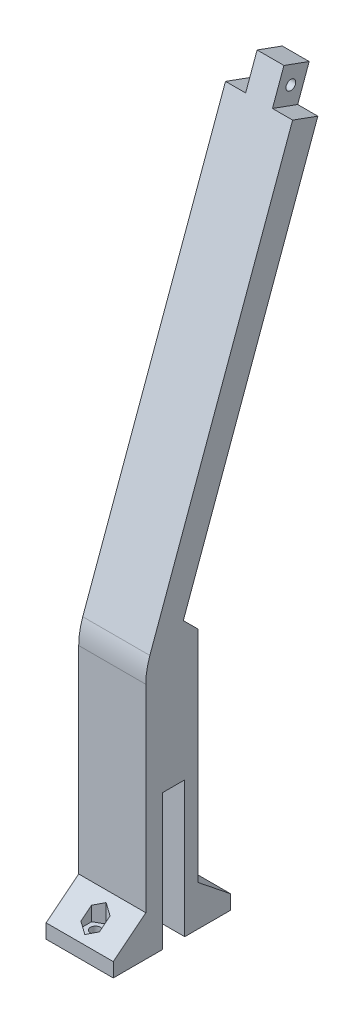
SolidWorks part; units mm, degrees
ref_plane "Front Plane" through (0, 0, 0) normal (0, 0, 1) x (1, 0, 0)
ref_plane "Top Plane" through (0, 0, 0) normal (0, 1, 0) x (1, 0, 0)
ref_plane "Right Plane" through (0, 0, 0) normal (1, 0, 0) x (0, 0, -1)
sketch "Sketch2" plane through (0, 0, 0) normal (1, 0, 0) x (0, 0, -1)
  line L0 (36.0729, 122.5) -> (-51.2799, -117.5)
  line L1 (-51.2799, -117.5) -> (-51.2799, -192)
  line L5 (-42.7665, -117.5) -> (42.7665, 117.5)
  line L6 (192.7665, 122.5) -> (36.0729, 122.5)
  line L7 (-42.7665, -117.5) -> (-35.6799, -117.5)
  line L9 (-39.6799, -151.5) -> (-46.2799, -151.5)
  line L10 (-46.2799, -151.5) -> (-46.2799, -192)
  line L13 (-35.6799, -117.5) -> (-35.6799, -192)
  line L14 (-35.6799, -192) -> (-39.6799, -192)
  line L15 (-39.6799, -192) -> (-39.6799, -151.5)
  line L16 (-51.2799, -192) -> (-46.2799, -192)
  line L18 (192.7665, 122.5) -> (192.7665, 117.5)
  line L19 (192.7665, 117.5) -> (42.7665, 117.5)
  dimension "D1" = 34
  dimension "D2" = 4
  dimension "D3" = 5
  dimension "D4" = 6.6
  dimension "D5" = 150
  dimension "D6" = 5
  dimension "D7" = 40.5
  dimension "D9" = 240
  dimension "D10" = 8
  dimension "D11" = 70
extrude "Boss-Extrude1" add sketch "Sketch2" along normal mid plane 20
chamfer "Chamfer1" distance 10 angle 45 1 edges at (0, -117.5, 42.7665) first distance on face at (0, -117.5, 39.2232)
sketch "Sketch6" plane through (10, 0, 0) normal (1, 0, 0) x (0, 0, -1)
  line L0 (-51.2799, -180) -> (-66.2799, -192)
  line L1 (-66.2799, -192) -> (-51.2799, -192)
  line L2 (-51.2799, -192) -> (-51.2799, -180)
  line L3 (-51.2799, -117.5) -> (-51.2799, -192) construction
  line L4 (-35.6799, -192) -> (-20.6799, -192)
  line L5 (-20.6799, -192) -> (-35.6799, -180)
  line L6 (-35.6799, -192) -> (-35.6799, -114.5866) construction
  line L7 (-35.6799, -180) -> (-35.6799, -192)
  dimension "D1" = 15
  dimension "D2" = 12
extrude "Boss-Extrude2" add sketch "Sketch6" against normal up to vertex (20 mm away) up to point (-10, -192, 51.2799)
sketch "Sketch7" plane through (0, -192, 0) normal (0, -1, 0) x (-1, 0, 0)
  line L0 (0, -66.2799) -> (0, -46.2799) construction
  line L1 (10, -66.2799) -> (-10, -66.2799) construction
  line L2 (-10, -46.2799) -> (10, -46.2799) construction
  line L3 (0, -20.6799) -> (0, -39.6799) construction
  line L4 (10, -20.6799) -> (-10, -20.6799) construction
  line L5 (-10, -39.6799) -> (10, -39.6799) construction
  circle A0 centre (0, -56.2799) radius 1.5
  circle A1 centre (0, -30.1799) radius 1.5
  dimension "D1" = 3
  dimension "D2" = 3
extrude "Cut-Extrude1" cut sketch "Sketch7" against normal blind 20
ref_plane "Plane1" through (0, -187, 0) normal (0, -1, 0) x (-1, 0, 0)
sketch "Sketch9" plane through (0, -187, 0) normal (0, -1, 0) x (-1, 0, 0)
  line L1 (2.75, -57.8676) -> (2.75, -54.6922)
  line L2 (2.75, -54.6922) -> (0, -53.1045)
  line L3 (0, -53.1045) -> (-2.75, -54.6922)
  line L4 (-2.75, -54.6922) -> (-2.75, -57.8676)
  line L5 (-2.75, -57.8676) -> (0, -59.4554)
  line L6 (0, -59.4554) -> (2.75, -57.8676)
  line L7 (2.75, -31.7676) -> (2.75, -28.5922)
  line L8 (2.75, -28.5922) -> (0, -27.0045)
  line L9 (0, -27.0045) -> (-2.75, -28.5922)
  line L10 (-2.75, -28.5922) -> (-2.75, -31.7676)
  line L11 (-2.75, -31.7676) -> (0, -33.3554)
  line L12 (0, -33.3554) -> (2.75, -31.7676)
  circle A0 centre (0, -56.2799) radius 2.75 construction
  circle A1 centre (0, -30.1799) radius 2.75 construction
  dimension "D1" = 5.5
  dimension "D2" = 5.5
extrude "Cut-Extrude3" cut sketch "Sketch9" against normal blind 20
fillet "Fillet5" radius 20 1 edges at (0, -117.5, 51.2799)
fillet "Fillet6" radius 10 1 edges at (0, 122.5, -36.0729)
sketch "Sketch10" plane through (10, 0, 0) normal (1, 0, 0) x (0, 0, -1)
  line L0 (-51.2799, -180) -> (-66.2799, -192) construction
  line L1 (-66.2799, -192) -> (-60.9799, -192)
  line L2 (-66.2799, -192) -> (-66.2799, -187.76)
  line L3 (-66.2799, -187.76) -> (-60.9799, -187.76)
  line L4 (-60.9799, -192) -> (-60.9799, -187.76)
  line L6 (-43.4799, -150) -> (-43.4799, -190.5) construction
  line L8 (-25.9799, -192) -> (-25.9799, -187.76)
  line L9 (-20.6799, -187.76) -> (-25.9799, -187.76)
  line L10 (-20.6799, -192) -> (-20.6799, -187.76)
  line L11 (-20.6799, -192) -> (-25.9799, -192)
  dimension "D1" = 35
extrude "Cut-Extrude4" cut sketch "Sketch10" against normal through all
sketch "Sketch11" plane through (0, 122.5, 0) normal (0, 1, 0) x (1, 0, 0)
  line L5 (-10, 43.075) -> (10, 43.075) construction
  line L6 (-10, 192.7665) -> (-6.25, 192.7665)
  line L7 (-10, 192.7665) -> (-10, 48.075)
  line L8 (-10, 48.075) -> (-6.25, 48.075)
  line L9 (-6.25, 192.7665) -> (-6.25, 48.075)
  line L10 (10, 192.7665) -> (6.25, 192.7665)
  line L11 (10, 192.7665) -> (10, 48.075)
  line L12 (10, 48.075) -> (6.25, 48.075)
  line L13 (6.25, 192.7665) -> (6.25, 48.075)
  dimension "D1" = 12.5
  dimension "D2" = 5
extrude "Cut-Extrude5" cut sketch "Sketch11" against normal through all
sketch "Sketch13" plane through (6.25, 0, 0) normal (1, 0, 0) x (0, 0, -1)
  line L0 (52.7665, 117.5) -> (37.7665, 103.7626)
  line L1 (192.7665, 117.5) -> (48.075, 117.5) construction
  line L2 (-40.098, -110.1685) -> (42.7665, 117.5) construction
  line L3 (37.7665, 103.7626) -> (42.7665, 117.5)
  line L4 (42.7665, 117.5) -> (52.7665, 117.5)
  dimension "D1" = 10
  dimension "D2" = 15
extrude "Boss-Extrude4" add sketch "Sketch13" against normal blind 12.5
sketch "Sketch12" plane through (0, 0, -192.7665) normal (0, 0, -1) x (-1, 0, 0)
  line L0 (-6.25, 117.5) -> (-6.25, 122.5) construction
  line L1 (-6.25, 120.75) -> (-4.25, 120.75)
  line L2 (-6.25, 120.75) -> (-6.25, 119.25)
  line L3 (-6.25, 119.25) -> (-4.25, 119.25)
  line L4 (-4.25, 120.75) -> (-4.25, 119.25)
  line L5 (0, 122.5) -> (0, 117.5) construction
  line L6 (-6.25, 122.5) -> (6.25, 122.5) construction
  line L7 (-6.25, 117.5) -> (6.25, 117.5) construction
  line L8 (4.25, 120.75) -> (4.25, 119.25)
  line L9 (6.25, 119.25) -> (4.25, 119.25)
  line L10 (6.25, 120.75) -> (6.25, 119.25)
  line L11 (6.25, 120.75) -> (4.25, 120.75)
  line L12 (-6.25, 122.5) -> (-6.25, 120.75) construction
  line L13 (-6.25, 117.5) -> (-6.25, 119.25) construction
  dimension "D1" = 1.75
  dimension "D2" = 1.5
  dimension "D3" = 2
extrude "Cut-Extrude6" cut sketch "Sketch12" against normal up to vertex (144.6915 mm away) up to point (10, 122.5, -48.075)
sketch "Sketch14" plane through (10, 0, 0) normal (1, 0, 0) x (0, 0, -1)
  line L0 (-7.5175, 2.7362) -> (0, 0)
  line L1 (33.6781, 115.9202) -> (-50.0738, -114.1861) construction
  line L2 (-7.5175, 2.7362) -> (28.5355, 129.4781)
  line L4 (28.5355, 129.4781) -> (208.2695, 129.4781)
  line L6 (0, 0) -> (208.2695, 117.5864)
  line L7 (208.2695, 117.5864) -> (208.2695, 129.4781)
extrude "Cut-Extrude7" cut sketch "Sketch14" against normal through all
sketch "Sketch15" plane through (0, 2.7362, 7.5175) normal (0, 0.342, 0.9397) x (1, 0, 0)
  line L0 (-10, 0) -> (10, 0) construction
  line L1 (-4, 0) -> (4, 0)
  line L2 (-4, 0) -> (-4, 10)
  line L3 (-4, 10) -> (4, 10)
  line L4 (4, 0) -> (4, 10)
  point P7 (0, 0)
  dimension "D1" = 8
  dimension "5" = 10
extrude "Boss-Extrude5" add sketch "Sketch15" against normal up to vertex (8 mm away) up to point (-10, 0, 0)
sketch "Sketch16" plane through (10, 0, 0) normal (1, 0, 0) x (0, 0, -1)
  line L0 (-3.7588, 1.3681) -> (-0.3386, 10.765) construction
  line L3 (0, 0) -> (-7.5175, 2.7362) construction
  line L4 (3.4202, 9.3969) -> (-4.0973, 12.1331) construction
  circle A0 centre (-2.0487, 6.0665) radius 1.45
  point P6 (-3.7588, 1.3681)
  point P9 (-2.0487, 6.0665)
  dimension "D2" = 2.9
extrude "Cut-Extrude9" cut sketch "Sketch16" against normal through all
